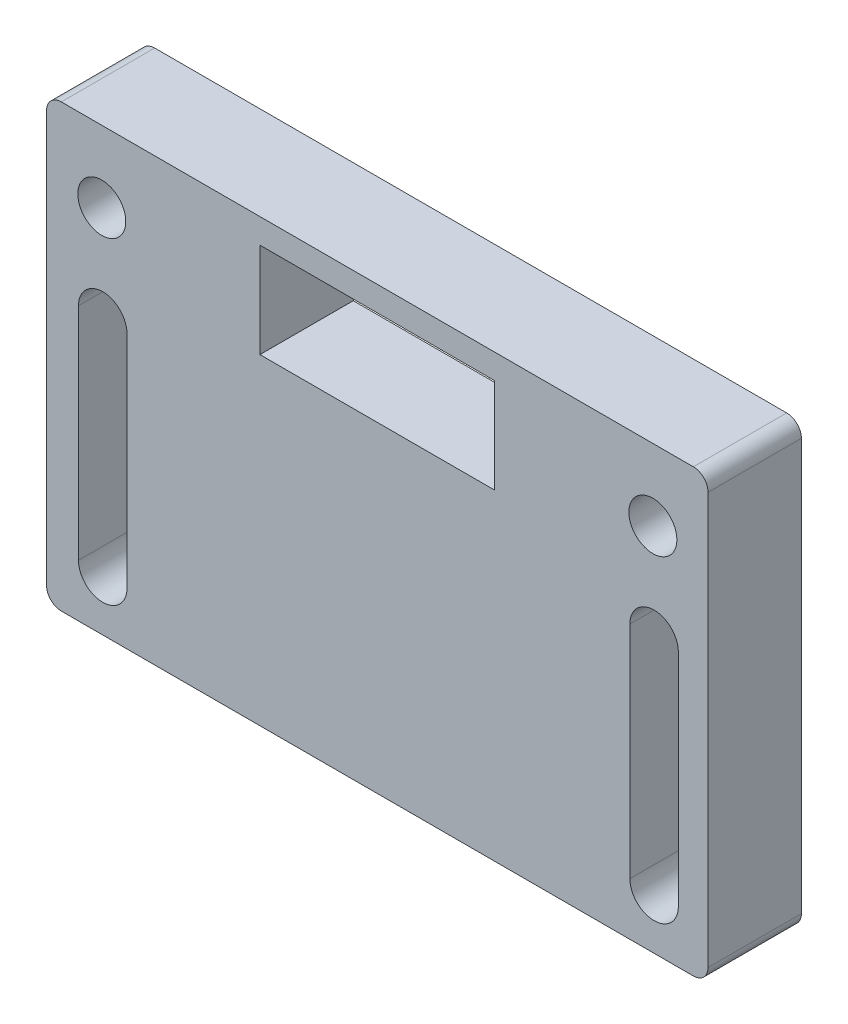
SolidWorks part; units mm, degrees
ref_plane "Front Plane" through (0, 0, 0) normal (0, 0, 1) x (1, 0, 0)
ref_plane "Top Plane" through (0, 0, 0) normal (0, 1, 0) x (1, 0, 0)
ref_plane "Right Plane" through (0, 0, 0) normal (1, 0, 0) x (0, 0, -1)
sketch "Sketch1" plane through (0, 0, 0) normal (0, 0, 1) x (1, 0, 0)
  line L0 (45, 0) -> (45, -60) construction
  line L1 (0, 0) -> (90, 0)
  line L2 (0, 0) -> (0, -60)
  line L3 (0, -60) -> (90, -60)
  line L4 (90, 0) -> (90, -60)
  line L5 (29.025, -3.3671) -> (29.025, -16.2671)
  line L6 (29.025, -16.2671) -> (60.975, -16.2671)
  line L7 (60.975, -16.2671) -> (60.975, -3.3671)
  line L9 (60.975, -3.3671) -> (45, -3.3671)
  line L10 (45, -3.3671) -> (29.025, -3.3671)
  dimension "D1" = 90
  dimension "D2" = 60
  dimension "D3" = 31.95
  dimension "D4" = 12.9
extrude "Boss-Extrude1" add sketch "Sketch1" along normal blind 12.7
sketch "Sketch2" plane through (0, 0, 0) normal (0, 0, -1) x (-1, 0, 0)
  line L0 (-82.49, -9.7171) -> (-7.51, -9.7171) construction
  line L1 (0, -9.7171) -> (-7.51, -9.7171)
  line L2 (-90, -60) -> (-90, 0) construction
  line L3 (-90, -9.7171) -> (-82.49, -9.7171)
  line L4 (0, 0) -> (0, -60) construction
  dimension "D1" = 7.51
  dimension "D2" = 7.51
  dimension "D3" = 74.98
hole_wizard "CSK for 1/4 Flat Head Machine Screw1" positions "Sketch3" profile "Sketch4" countersink size "1/4" standard "ANSI Inch" end condition through all
sketch "Sketch3" plane through (0, 0, 0) normal (0, 0, -1) x (-1, 0, 0)
  point P0 (-82.49, -9.7171)
  point P3 (-7.51, -9.7171)
sketch "Sketch4" plane through (82.49, -9.7171, 0) normal (1, 0, 0) x (0, 1, 0)
  line L0 (0, 0) -> (0, 12.7)
  line L1 (0, 12.7) -> (3.2639, 12.7)
  line L2 (3.2639, 12.7) -> (3.2639, 3.6524)
  line L3 (3.2639, 3.6524) -> (6.4389, 0)
  line L5 (6.4389, 0) -> (0, 0)
  line L6 (-3.2639, 3.6524) -> (-6.4389, 0) construction
  line L11 (0, -6.35) -> (0, 107.95) construction
  dimension "Thru Hole Dia." = 6.5278
  dimension "Thru Hole Depth" = 12.7
  dimension "Near C'Sink Dia." = 12.8778
  dimension "Near C'Sink Angle" = 82
fillet "Fillet1" radius 2 4 edges at (0, -60, 6.35) (0, 0, 6.35) (90, 0, 6.35) (90, -60, 6.35)
sketch "Sketch5" plane through (0, 0, 0) normal (0, 0, -1) x (-1, 0, 0)
  line L0 (-10.9392, -22.8474) -> (-10.9392, -52.8474)
  line L1 (-4.3392, -52.8474) -> (-4.3392, -22.8474)
  line L2 (-10.9392, -52.8474) -> (-79.3592, -52.8474) construction
  line L3 (-79.3592, -52.8474) -> (-79.3592, -22.8474)
  line L4 (-85.9592, -52.8474) -> (-85.9592, -22.8474)
  line L5 (0, -2) -> (0, -58) construction
  line L6 (-2, -60) -> (-88, -60) construction
  arc A0 (-10.9392, -52.8474) -> (-4.3392, -52.8474) centre (-7.6392, -52.8474) ccw
  arc A1 (-4.3392, -22.8474) -> (-10.9392, -22.8474) centre (-7.6392, -22.8474) ccw
  arc A2 (-85.9592, -52.8474) -> (-79.3592, -52.8474) centre (-82.6592, -52.8474) ccw
  arc A3 (-79.3592, -22.8474) -> (-85.9592, -22.8474) centre (-82.6592, -22.8474) ccw
  dimension "D1" = 3.3
  dimension "D4" = 3.3
  dimension "D7" = 7.1526
  dimension "D2" = 30
  dimension "D3" = 68.42
  dimension "D5" = 30
  dimension "D6" = 4.3392
extrude "Cut-Extrude1" cut sketch "Sketch5" against normal through all
